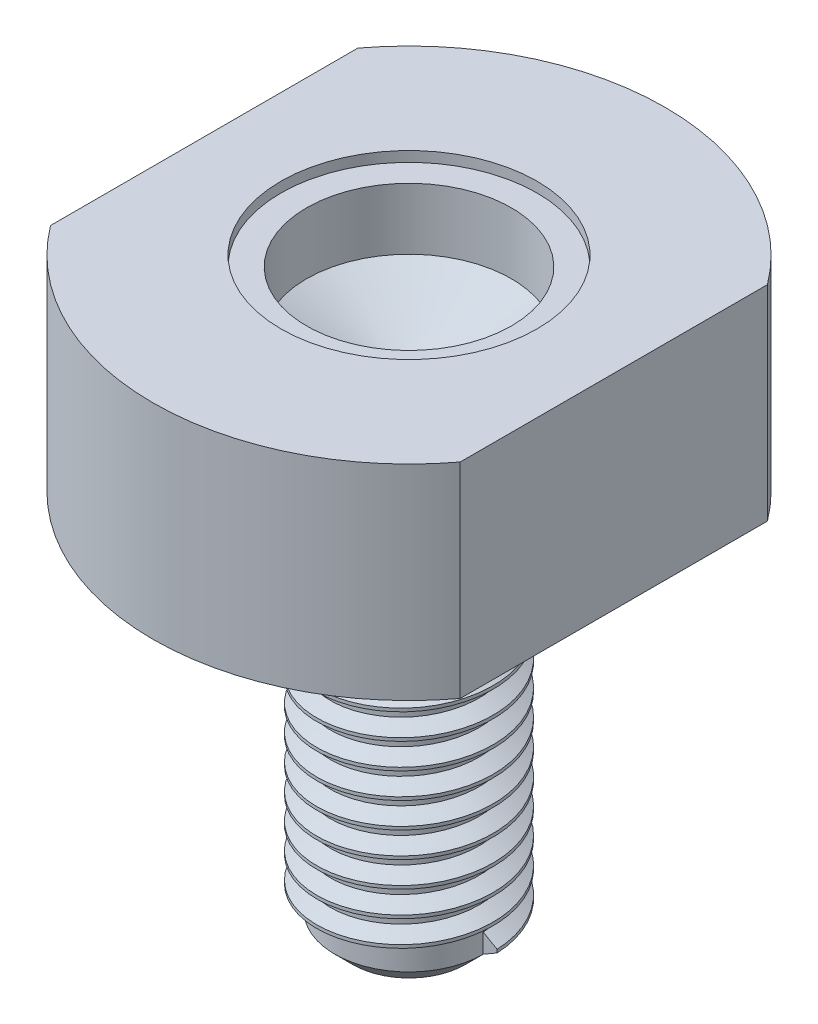
SolidWorks part; units mm, degrees
ref_plane "Płaszczyzna przednia" through (0, 0, 0) normal (0, 0, 1) x (1, 0, 0)
ref_plane "Płaszczyzna górna" through (0, 0, 0) normal (0, 1, 0) x (1, 0, 0)
ref_plane "Płaszczyzna prawa" through (0, 0, 0) normal (1, 0, 0) x (0, 0, -1)
sketch "Szkic1" plane through (0, 0, 0) normal (0, 0, 1) x (1, 0, 0)
  line L0 (0, 0) -> (0, 11.45)
  line L1 (0, 0) -> (1.1, 0)
  line L2 (1.1, 0) -> (1.45, 0.35)
  line L3 (1.45, 0.35) -> (1.45, 4.95)
  line L4 (1.45, 4.95) -> (1.1, 4.95)
  line L5 (1.1, 4.95) -> (1.1, 7.45)
  line L6 (1.1, 7.45) -> (5, 7.45)
  line L7 (5, 7.45) -> (5, 11.45)
  line L8 (5, 11.45) -> (0, 11.45)
  line L9 (0, 9.05) -> (2, 10.05)
  line L10 (2, 10.05) -> (2, 11.25)
  line L11 (2, 11.25) -> (2.5, 11.25)
  line L12 (2.5, 11.25) -> (2.5, 11.45)
  point P15 (2, 9.4117)
  dimension "D1" = 0.2
  dimension "D2" = 5
  dimension "D3" = 2
  dimension "D4" = 2.5
  dimension "D5" = 2.4
  dimension "D6" = 1.1
  dimension "D7" = 4
  dimension "D8" = 2.5
  dimension "D9" = 4.6
  dimension "D10" = 1.2
  dimension "D11" = 1.45
  dimension "D12" = 135
  dimension "D13" = 1.1
revolve "Obrót1" add sketch "Szkic1" angle 360 about L0 region at (0.1249, 4.525, 0)
sketch "Szkic2" plane through (0, 0, 0) normal (0, 0, 1) x (1, 0, 0)
  line L0 (0, 0) -> (0, 11.45) construction
  line L1 (5, 11.45) -> (-5, 11.45) construction
  line L2 (-5, 7.45) -> (5, 7.45) construction
  line L3 (-4, 7.45) -> (-5, 7.45)
  line L4 (-4, 7.45) -> (-4, 11.45)
  line L5 (-4, 11.45) -> (-5, 11.45)
  line L6 (-5, 7.45) -> (-5, 11.45)
  line L7 (-4.5, 11.45) -> (-4.5, 7.45) construction
  line L8 (-4, 9.45) -> (-5, 9.45) construction
  line L9 (4, 9.45) -> (5, 9.45) construction
  line L10 (4.5, 11.45) -> (4.5, 7.45) construction
  line L11 (5, 7.45) -> (5, 11.45)
  line L12 (4, 11.45) -> (5, 11.45)
  line L13 (4, 7.45) -> (4, 11.45)
  line L14 (4, 7.45) -> (5, 7.45)
  point P19 (4.5, 9.45)
  point P169 (-4.5, 9.45)
  dimension "D1" = 4
extrude "Wytnij-wyciągnięcie1" cut sketch "Szkic2" against normal mid plane 10
thread "Gwint1" pitch 0.5 method extrude profile "Profil gwintu2" start angle 0, offset 0, length 0, pitch 0.5, diameter 2.9
ref_plane "Płaszczyzna2" through (1.45, 0.35, 0) normal (0, 0, 1) x (1, 0, 0)
sketch "Profil gwintu2" plane through (1.45, 0.35, 0) normal (0, 0, 1) x (1, 0, 0)
  line L0 (0, 0) -> (0, 0.5) construction
  line L1 (0, 0) -> (0.2706, 0.1562)
  line L2 (0.2706, 0.1562) -> (0.2706, 0.2187)
  line L3 (0.2706, 0.2187) -> (0, 0.375)
  line L4 (0.2706, 0.1875) -> (0, 0.1875) construction
  line L11 (0, 0) -> (0, 0.375)
  point P2 (0, 0)
  dimension "Pitch" = 0.5
  dimension "Profile_Angle" = 60
  dimension "Profile_Land" = 0.0625
  dimension "Profile_Height" = 0.2706
